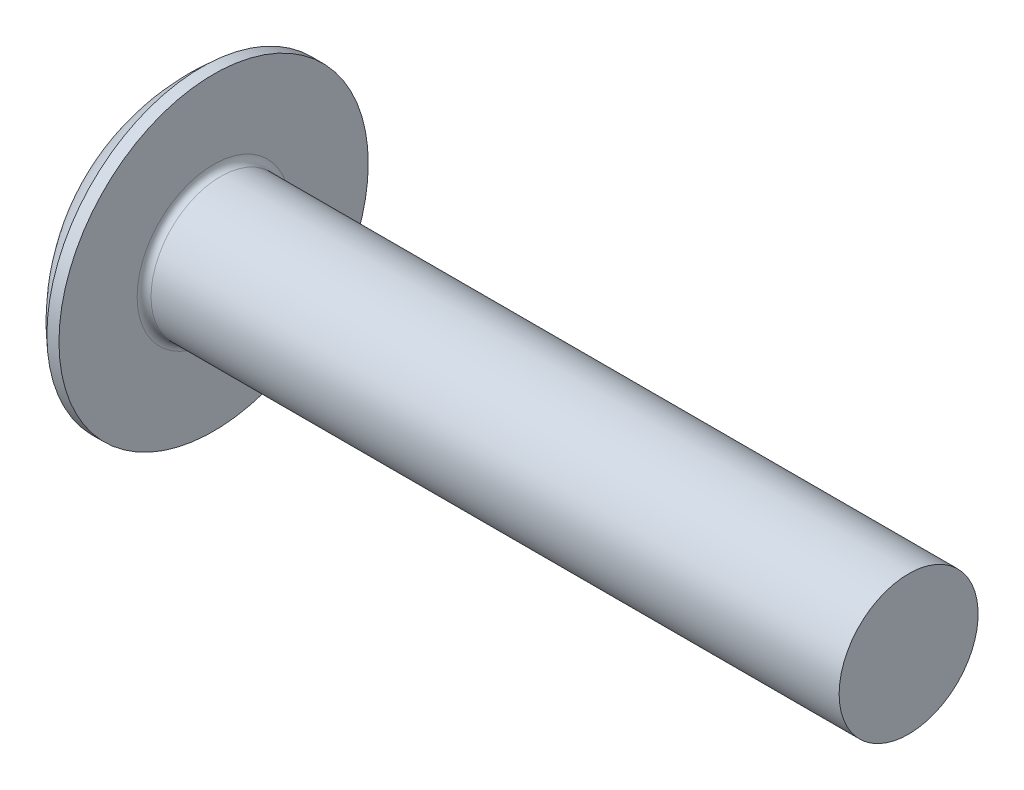
SolidWorks part; units mm, degrees
ref_plane "Front Plane" through (0, 0, 0) normal (0, 0, 1) x (1, 0, 0)
ref_plane "Top Plane" through (0, 0, 0) normal (0, 1, 0) x (1, 0, 0)
ref_plane "Right Plane" through (0, 0, 0) normal (1, 0, 0) x (0, 0, -1)
sketch "BodySke" plane through (0, 0, 0) normal (0, 0, 1) x (1, 0, 0)
  line L0 (0, 0) -> (120.5141, 0) construction
  line L1 (0, 0) -> (0, 50.5629) construction
  line L2 (4.8, 8.9) -> (4.8, 4)
  line L3 (4.8, 4) -> (44.8, 4)
  line L4 (44.8, 4) -> (44.8, 0)
  line L5 (0, 0) -> (44.8, 0)
  line L6 (4.8, 8.9) -> (4.1053, 8.9)
  line L7 (6.05, 10.4217) -> (6.05, -3.1786) construction
  line L8 (14.8, 9.5609) -> (14.8, -6.7938) construction
  arc A0 (0, 0) -> (4.1053, 8.9) centre (11.7, 0) cw
  point P14 (44.8, 3.3095)
  dimension "Thread_minor" = 6.619
  dimension "Advance" = 1.25
revolve "BaseBody" add sketch "BodySke" angle 360 about L0
cosmetic thread "ThreadCosmetic" [suppressed] parameters "Thread_minor"=6.619
fillet "Fillet1" radius 0.4 1 edges at (4.8, 0, 4)
sketch "SlotSke" plane through (0, 0, 0) normal (1, 0, 0) x (0, 0, -1)
  line L1 (8.9, 0.8) -> (-8.9, 0.8)
  line L2 (8.9, 0.8) -> (8.9, -0.8)
  line L3 (8.9, -0.8) -> (-8.9, -0.8)
  line L4 (-8.9, 0.8) -> (-8.9, -0.8)
  dimension "D1" = 17.8
  dimension "D2" = 8.9
  dimension "D4" = 0.8
extrude "Slot" cut sketch "SlotSke" along normal blind 2.4
sketch "ThdSchSke" plane through (0, 0, 0) normal (0, 0, 1) x (1, 0, 0)
  line L0 (0, 0) -> (54.7976, 0) construction
  line L1 (44.4013, 4.7973) -> (44.4013, 4)
  line L2 (44.4013, 4.7973) -> (45.1987, 4.7973)
  line L3 (45.1987, 4.7973) -> (45.1987, 4)
  line L4 (45.1987, 4) -> (44.8, 3.3095)
  line L5 (44.8, 3.3095) -> (44.4013, 4)
  line L6 (4.8, 4) -> (44.8, 4) construction
revolve "ThreadSchematic" [suppressed] cut sketch "ThdSchSke" angle 360 about L0
pattern_linear "ThdSchPat" [suppressed] count 24 along (-1, 0, 0) of bodies 103
equation "\"Thread_minor@ThreadCosmetic\" = \"Thread_minor@BodySke\""
equation "\"D1@SlotSke\" = \"Head_dia@BodySke\""
equation "\"D2@SlotSke\" = \"D1@SlotSke\" / 2"
equation "\"D4@SlotSke\" = \"Slot_width@SlotSke\" / 2"
equation "\"Advance@ThdSchPat\" = \"Advance@BodySke\""
equation "\"D1@ThdSchPat\" =  int( \"Thread_length@BodySke\" / \"Advance@BodySke\" ) "
